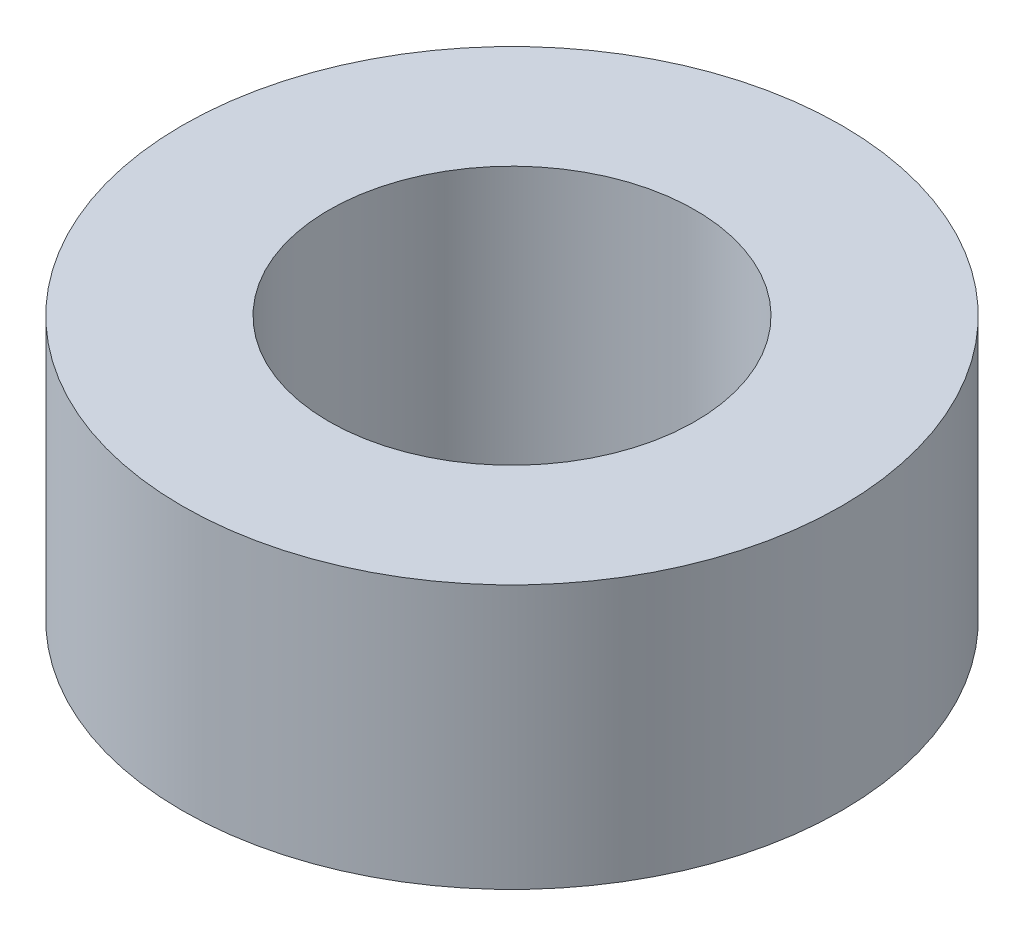
SolidWorks part; units mm, degrees
ref_plane "Front Plane" through (0, 0, 0) normal (0, 0, 1) x (1, 0, 0)
ref_plane "Top Plane" through (0, 0, 0) normal (0, 1, 0) x (1, 0, 0)
ref_plane "Right Plane" through (0, 0, 0) normal (1, 0, 0) x (0, 0, -1)
sketch "Sketch1" plane through (0, 0, 0) normal (0, 1, 0) x (1, 0, 0)
  circle A0 centre (0, 0) radius 22.5
  dimension "FLANGE_OD" = 45
extrude "Boss-Extrude1" add sketch "Sketch1" along normal blind 18
sketch "Sketch2" plane through (0, 0, 0) normal (0, 1, 0) x (1, 0, 0)
  circle A0 centre (0, 0) radius 12.5
  dimension "BORE_D" = 25
extrude "Cut-Extrude1" cut sketch "Sketch2" along normal through all
sketch "Sketch3" plane through (0, 18, 0) normal (0, 1, 0) x (1, 0, 0)
  circle A0 centre (0, 0) radius 7.5301 construction
  circle A1 centre (-7.5301, 0) radius 1.5083
  dimension "BOLT_D" = 3.0167
  dimension "BOLT_PCD" = 15.0602
extrude "Cut-Extrude2" cut sketch "Sketch3" against normal blind 11.5377 rebuild error yes
pattern_circular "CirPattern1" count 4 over 360 rebuild error yes
